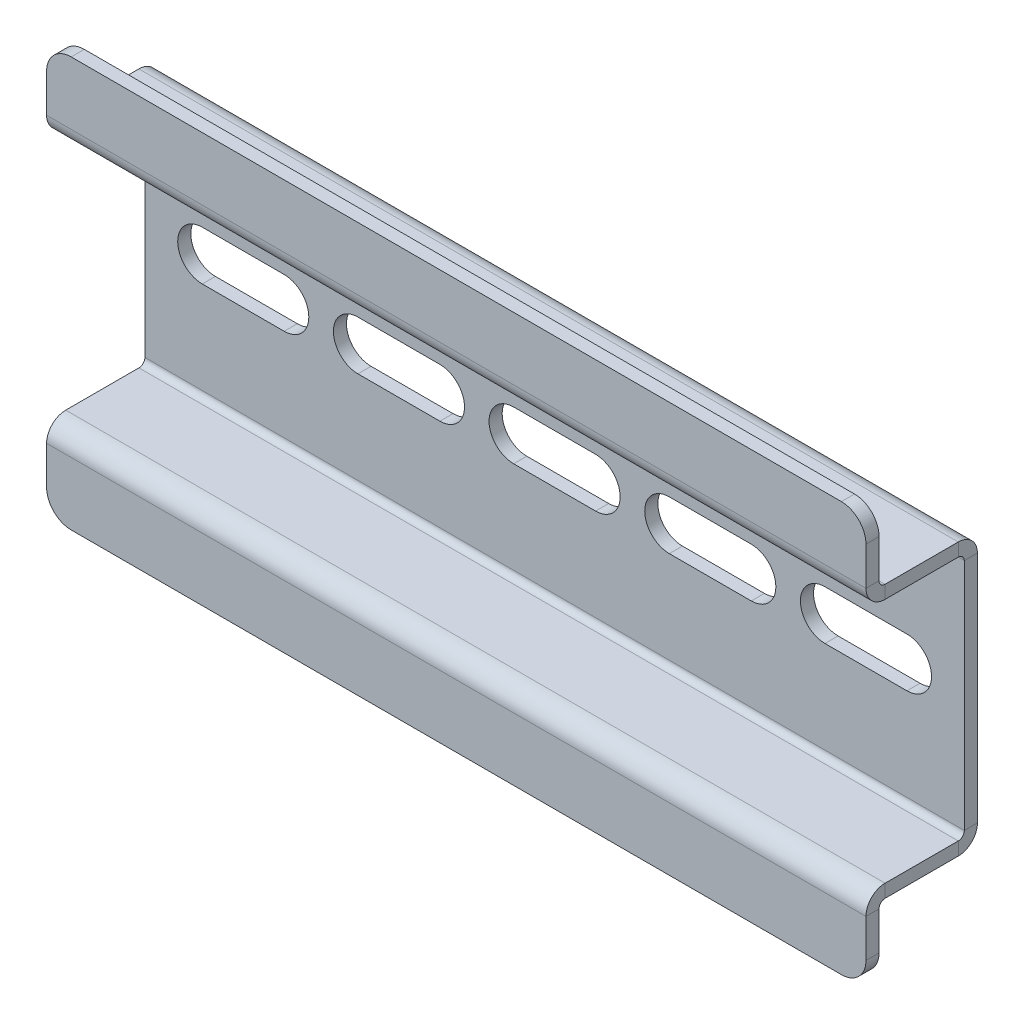
SolidWorks part; units mm, degrees
note: The reader was unsure of these and kept them because the rebuilt part matched: flange length of "边线-法兰1", "边线-法兰2".
ref_plane "前视基准面" through (0, 0, 0) normal (0, 0, 1) x (1, 0, 0)
ref_plane "上视基准面" through (0, 0, 0) normal (0, 1, 0) x (1, 0, 0)
ref_plane "右视基准面" through (0, 0, 0) normal (1, 0, 0) x (0, 0, -1)
sketch "草图1" plane through (0, 0, 0) normal (0, 0, 1) x (1, 0, 0)
  line L0 (-133.4308, 0) -> (152.3304, 0) construction
  line L1 (0, 101.6796) -> (0, -102.1836) construction
  line L3 (-50, 15) -> (50, 15)
  line L4 (-50, 15) -> (-50, -15)
  line L5 (-50, -15) -> (50, -15)
  line L6 (50, 15) -> (50, -15)
  dimension "D1" = 100
  dimension "D2" = 30
sheet metal parameters "钣金1" thickness 1.6 parameters "D1"=0.7366
base flange "基体-法兰1" sketch "草图1" thickness 1.6 reverse thickness direction no parameters "D1"=0.7366
edge flange "边线-法兰1" sketch "草图9" flange profiles "草图9", "草图10" flange angle 90 flange length 12 flange position material outside bend radius 0.7366 thickness 1.6 relief rectangular parameters "D6"=10, "D8"=1
sketch "草图9" plane through (0, 15, 0) normal (0, 1, 0) x (-1, 0, 0)
  line L2 (-50, 0) -> (-50, 10.4)
  line L3 (-50, 10.4) -> (50, 10.4)
  line L4 (50, 10.4) -> (50, 0)
  line L5 (-50, 0) -> (50, 0) construction
  line L6 (-50, 0) -> (50, 0)
sketch "草图10" plane through (0, -15, 0) normal (0, -1, 0) x (1, 0, 0)
  line L0 (-50, 0) -> (50, 0) construction
  line L1 (-50, 0) -> (50, 0)
  line L2 (-50, 0) -> (-50, 10.4)
  line L3 (-50, 10.4) -> (50, 10.4)
  line L4 (50, 10.4) -> (50, 0)
bend "边线折弯1" bend radius 0.7366 bend angle 90 parameters "D5"=1
bend "边线折弯2" bend radius 0.7366 bend angle 90 parameters "D5"=2
edge flange "边线-法兰2" sketch "草图15" flange profiles "草图15", "草图16" flange angle 90 flange length 10 flange position material outside bend radius 0.7366 thickness 1.6 relief rectangular parameters "D6"=10, "D8"=1
sketch "草图15" plane through (0, 16.6, 10.4) normal (0, 0, 1) x (1, 0, 0)
  line L2 (-50, 0) -> (-50, 8.4)
  line L3 (-50, 8.4) -> (50, 8.4)
  line L4 (50, 8.4) -> (50, 0)
  line L5 (-50, 0) -> (50, 0) construction
  line L6 (-50, 0) -> (50, 0)
sketch "草图16" plane through (0, -16.6, 10.4) normal (0, 0, 1) x (-1, 0, 0)
  line L0 (-50, 0) -> (50, 0) construction
  line L1 (-50, 0) -> (50, 0)
  line L2 (-50, 0) -> (-50, 8.4)
  line L3 (-50, 8.4) -> (50, 8.4)
  line L4 (50, 8.4) -> (50, 0)
bend "边线折弯3" bend radius 0.7366 bend angle 90 parameters "D5"=3
bend "边线折弯4" bend radius 0.7366 bend angle 90 parameters "D5"=4
sketch "草图18" plane through (0, 0, 0) normal (0, 0, 1) x (1, 0, 0)
  line L0 (50, 25) -> (47, 25)
  line L5 (50, 25) -> (50, 22)
  line L6 (-47, 25) -> (-50, 25)
  line L7 (-50, 25) -> (-50, 22)
  line L8 (-50, -22) -> (-50, -25)
  line L9 (-50, -25) -> (-47, -25)
  line L10 (47, -25) -> (50, -25)
  line L11 (50, -25) -> (50, -22)
  arc A0 (47, -25) -> (50, -22) centre (47, -22) ccw
  arc A1 (-47, -25) -> (-50, -22) centre (-47, -22) cw
  arc A2 (-50, 22) -> (-47, 25) centre (-47, 22) cw
  arc A3 (50, 22) -> (47, 25) centre (47, 22) ccw
  point P13 (-50, -25)
  point P18 (50, 25)
  dimension "D1" = 3
extrude "切除-拉伸1" cut sketch "草图18" along normal through all normal cut yes
sketch "草图19" plane through (0, 0, -1.6) normal (0, 0, -1) x (-1, 0, 0)
  line L0 (-43, 0) -> (-33, 0) construction
  line L1 (133.4308, 0) -> (-152.3304, 0) construction
  line L2 (-43, 3) -> (-33, 3)
  line L3 (-43, -3) -> (-33, -3)
  line L4 (-50, -14.2634) -> (-50, 14.2634) construction
  line L5 (-24, 0) -> (-14, 0) construction
  line L6 (-24, 3) -> (-14, 3)
  line L7 (-24, -3) -> (-14, -3)
  line L8 (-5, 0) -> (5, 0) construction
  line L9 (-5, 3) -> (5, 3)
  line L10 (-5, -3) -> (5, -3)
  line L11 (14, 0) -> (24, 0) construction
  line L12 (14, 3) -> (24, 3)
  line L13 (14, -3) -> (24, -3)
  line L14 (33, 0) -> (43, 0) construction
  line L15 (33, 3) -> (43, 3)
  line L16 (33, -3) -> (43, -3)
  arc A0 (-43, 3) -> (-43, -3) centre (-43, 0) ccw
  arc A1 (-33, -3) -> (-33, 3) centre (-33, 0) ccw
  arc A2 (-24, 3) -> (-24, -3) centre (-24, 0) ccw
  arc A3 (-14, -3) -> (-14, 3) centre (-14, 0) ccw
  arc A4 (-5, 3) -> (-5, -3) centre (-5, 0) ccw
  arc A5 (5, -3) -> (5, 3) centre (5, 0) ccw
  arc A6 (14, 3) -> (14, -3) centre (14, 0) ccw
  arc A7 (24, -3) -> (24, 3) centre (24, 0) ccw
  arc A8 (33, 3) -> (33, -3) centre (33, 0) ccw
  arc A9 (43, -3) -> (43, 3) centre (43, 0) ccw
  point P4 (-38, 0)
  point P9 (-50, 0)
  point P16 (-19, 0)
  point P23 (0, 0)
  point P30 (19, 0)
  point P37 (38, 0)
  dimension "D1" = 3
  dimension "D2" = 10
  dimension "D3" = 7
  dimension "D4" = 5
extrude "切除-拉伸2" cut sketch "草图19" against normal through all normal cut yes
flat pattern "平板型式1" [suppressed]
sketch "折弯-线1" plane through (0, 0, 0) normal (0, 1, 0) x (-1, 0, 0)
sketch3d "边界框1" [suppressed]
  line L0 (0, 0, 0) -> (-100, 0, 0) construction
  line L1 (0, 30, 0) -> (-100, 30, 0) construction
  line L2 (0, 0, 0) -> (0, 30, 0) construction
  line L3 (-100, 0, 0) -> (-100, 30, 0) construction
bend of the flat pattern "展开-<边线折弯1>1"
bend of the flat pattern "展开-<边线折弯2>1"
bend of the flat pattern "展开-<边线折弯3>2"
bend of the flat pattern "展开-<边线折弯4>2"
